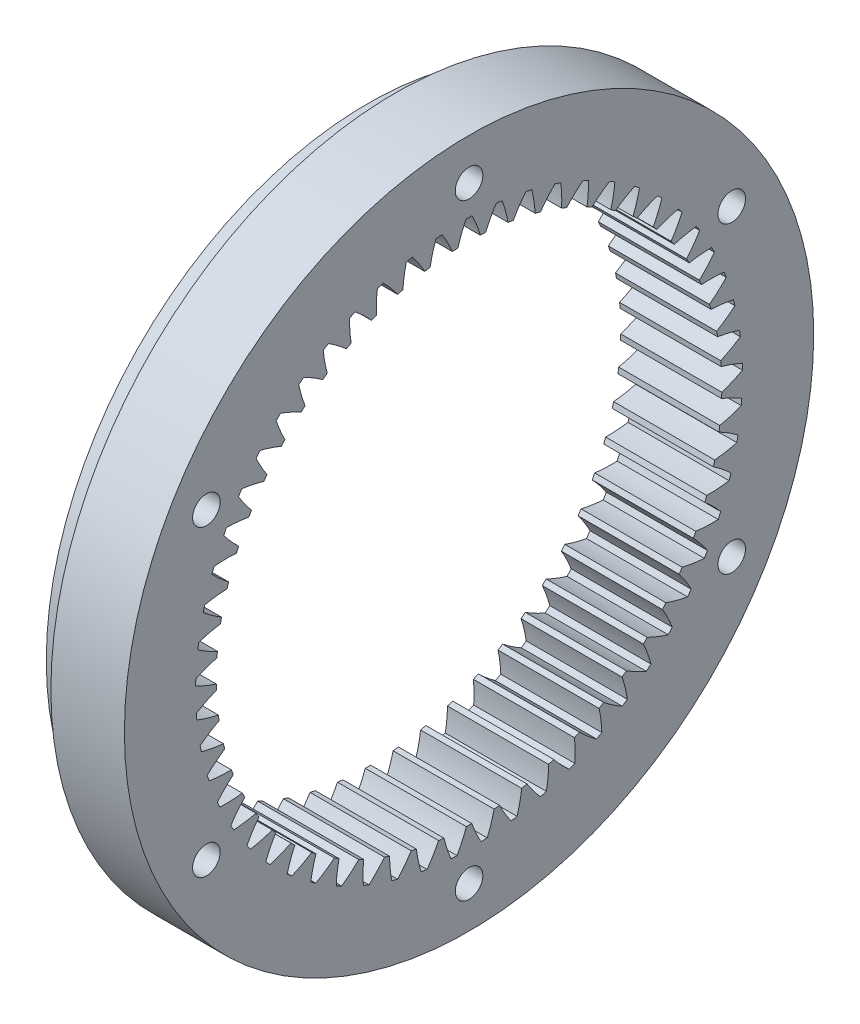
SolidWorks part; units mm, degrees
ref_plane "Plane1" through (0, 0, 0) normal (0, 0, 1) x (1, 0, 0)
ref_plane "Plane2" through (0, 0, 0) normal (0, 1, 0) x (1, 0, 0)
ref_plane "Plane3" through (0, 0, 0) normal (1, 0, 0) x (0, 0, -1)
sketch "HoldingSke" plane through (0, 0, 0) normal (0, 1, 0) x (1, 0, 0)
  line L0 (0, 0) -> (0.5446, -0.8387)
  line L1 (-15, 0) -> (100, 0) construction
  line L2 (0, 0) -> (-2.1039, 2.3779)
  line L3 (0, 0) -> (-11.863, 4.5341)
  line L4 (0, 0) -> (4.7035, 7.2428)
  line L5 (0, 0) -> (-23.7986, -8.8762)
  line L6 (0, 0) -> (-10.5278, -7.1032)
  line L7 (-2.1039, 2.3779) -> (3.3635, 27.1825)
  line L8 (-76.2, 3.3779) -> (-54.61, 3.3779)
  line L9 (-71.009, 38.7566) -> (-53.1078, 45.2721)
  line L10 (-76.2, 71.12) -> (104.1128, 71.12)
  line L11 (0, 0) -> (-11, 0)
  line L12 (-76.2, 101.6) -> (-76.162, 101.6)
  line L13 (24.9733, 27.94) -> (52.9518, 28.4284)
  line L14 (24.9733, 27.94) -> (24.9743, 27.94)
  line L15 (24.9733, 27.94) -> (100.4006, 29.5858)
  circle A0 centre (0, 0) radius 35
  circle A1 centre (0, 0) radius 12.7
  circle A2 centre (0, 0) radius 12.7
  dimension "Num_teeth" = 57
  dimension "Pitch_radius" = 180.3128
  dimension "Width" = 11
  dimension "Diameter" = 70
sketch "BasProSke" plane through (0, 0, 0) normal (0, 1, 0) x (1, 0, 0)
  line L0 (-10, 0) -> (60, 0) construction
  line L1 (0, 27.5) -> (0, 35)
  line L2 (0, 27.5) -> (11, 27.5)
  line L3 (11, 27.5) -> (11, 35)
  line L4 (11, 35) -> (0, 35)
  dimension "Thickness" = 11
  dimension "Diameter" = 70
revolve "Base-Revolve" add sketch "BasProSke" angle 360 about L0
sketch "TooCutSke" plane through (0, 0, 0) normal (1, 0, 0) x (0, 0, -1)
  line L3 (0.8803, 28.4864) -> (0.8803, 53.6633) construction
  line L4 (0, 0) -> (0, 59.563) construction
  line L5 (0, 0) -> (-3.764, 68.2237) construction
  line L6 (-12.4511, 23.4528) -> (36.4576, 26.1512) construction
  circle A0 centre (0, 0) radius 28.5 construction
  circle A1 centre (0, 0) radius 29.751 construction
  circle A2 centre (0, 0) radius 24.1031 construction
  circle A3 centre (0, 0) radius 27.4746 construction
  arc A4 (1.2277, 27.4472) -> (0.3325, 29.7491) centre (-12.4511, 23.4528) ccw
  arc A5 (1.2277, 27.4472) -> (-1.2277, 27.4472) centre (0, 0) ccw
  arc A6 (0.3325, 29.7491) -> (-0.3325, 29.7491) centre (0, 0) ccw
  arc A7 (-0.3325, 29.7491) -> (-1.2277, 27.4472) centre (12.4511, 23.4528) ccw
extrude "ToothCut" cut sketch "TooCutSke" along normal through all
fillet "Breaks" [suppressed] radius 0.1
fillet "RootFillets" [suppressed] radius 0.251
pattern_circular "TeethCuts" count 57 every 6.316 about axis through (-10, 0, 0) along (1, 0, 0) of "RootFillets", "Breaks", "ToothCut"
sketch "Sketch1" plane through (11, 0, 0) normal (1, 0, 0) x (0, 0, -1)
  circle A0 centre (0, 0) radius 37.5
  circle A1 centre (0, 0) radius 35 construction
  circle A2 centre (0, 0) radius 35
  dimension "D1" = 75
extrude "Boss-Extrude1" add sketch "Sketch1" against normal blind 8
sketch "Sketch2" plane through (0, 0, 0) normal (-1, 0, 0) x (0, 0, 1)
  circle A1 centre (0, 0) radius 33 construction
  circle A3 centre (28.5788, 16.5) radius 1.5
  circle A5 centre (28.5788, -16.5) radius 1.5
  circle A7 centre (0, -33) radius 1.5
  circle A9 centre (-28.5788, -16.5) radius 1.5
  circle A11 centre (-28.5788, 16.5) radius 1.5
  circle A12 centre (0, 33) radius 1.5
  point P14 (0, 0)
  dimension "D1" = 3
  dimension "D2" = 66
  dimension "D3" = 6
extrude "Cut-Extrude1" cut sketch "Sketch2" against normal through all
equation "' \"Module@HoldingSke\" = 6.35"
equation "' \"Num_teeth@HoldingSke\" = 24"
equation "' \"Ap@HoldingSke\" =  14.5"
equation "' \"Ap@HoldingSke\" = 14.5"
equation "' \"Width@HoldingSke\" = 12"
equation "' \"Diameter@HoldingSke\" = 8 * 25.4"
equation "' \"Show_teeth@HoldingSke\" = 100"
equation "' \"Backlash@HoldingSke\" = 0.009 * 25.4"
equation "' \"Addendum_fac@HoldingSke\" = 1.0"
equation "' \"Dedendum_fac@HoldingSke\" = 1.25"
equation "' \"Dedendum_add@HoldingSke\" = 0.00005 * 25.4"
equation "' \"Clearance_fac@HoldingSke\" = 0.25"
equation "\"Pitch@HoldingSke\" = 1 / \"Module@HoldingSke\" "
equation "\"Overcut_dia@TooCutSke\" = (\"Num_teeth@HoldingSke\" - 2 * \"Addendum_fac@HoldingSke\") / \"Pitch@HoldingSke\" - 0.002 * 25.4"
equation "\"Pitch_dia@TooCutSke\" = \"Num_teeth@HoldingSke\" / \"Pitch@HoldingSke\""
equation "\"Base_dia@TooCutSke\" = \"Num_teeth@HoldingSke\" / \"Pitch@HoldingSke\" * cos((\"Ap@HoldingSke\"  * 3.14159265 / 180)) * 0.90"
equation "\"Root_dia@TooCutSke\" = \"Num_teeth@HoldingSke\"  / \"Pitch@HoldingSke\" + 2 *  \"Dedendum_fac@HoldingSke\"/ \"Pitch@HoldingSke\" + \"Dedendum_add@HoldingSke\" * 2"
equation "\"Half_ang@TooCutSke\" = 180 / \"Num_teeth@HoldingSke\""
equation "\"Half_CT@TooCutSke\" = \"Num_teeth@HoldingSke\" / \"Pitch@HoldingSke\" * sin((3.14159265 / 2 / \"Num_teeth@HoldingSke\")) / 2 + 10 * \"Backlash@HoldingSke\" / 4"
equation "\"Flank_rad@TooCutSke\" = \"Num_teeth@HoldingSke\" / \"Pitch@HoldingSke\" / 4"
equation "\"Radius@RootFillets\"= \"Clearance_fac@HoldingSke\" / \"Pitch@HoldingSke\" + \"Dedendum_add@HoldingSke\""
equation "\"Break_rad@Breaks\" = 0.02 / \"Pitch@HoldingSke\" * 5"
equation "\"Num_teeth@TeethCuts\" = int( \"Show_teeth@HoldingSke\" ) + 1"
equation "\"Num_teeth@TeethCuts\" = ((sgn( \"Num_teeth@TeethCuts\" - \"Num_teeth@HoldingSke\" )-1)*( \"Num_teeth@TeethCuts\" - \"Num_teeth@HoldingSke\" ))/-2+ \"Num_teeth@HoldingSke\""
equation "\"Num_teeth@TeethCuts\" = ((sgn( \"Num_teeth@TeethCuts\" - 2.0)+1)*( \"Num_teeth@TeethCuts\" - 2.0))/2 +2.0"
equation "\"Angle@TeethCuts\" = 360.0 / \"Num_teeth@HoldingSke\""
equation "\"Diameter@BasProSke\" = \"Num_teeth@HoldingSke\"  / \"Pitch@HoldingSke\" + 2 *  \"Dedendum_fac@HoldingSke\"/ \"Pitch@HoldingSke\" + \"Dedendum_add@HoldingSke\" * 2 + 0.002 * 25.4"
equation "\"Diameter@BasProSke\" = ((sgn( \"Diameter@BasProSke\"  - \"Diameter@HoldingSke\" )+1)*( \"Diameter@BasProSke\"  - \"Diameter@HoldingSke\" ))/2 + \"Diameter@HoldingSke\""
equation "\"Inside_diameter@BasProSke\" =  (\"Num_teeth@HoldingSke\" - 2 * \"Addendum_fac@HoldingSke\") / \"Pitch@HoldingSke\" "
equation "\"Thickness@BasProSke\"  = \"Width@HoldingSke\""
